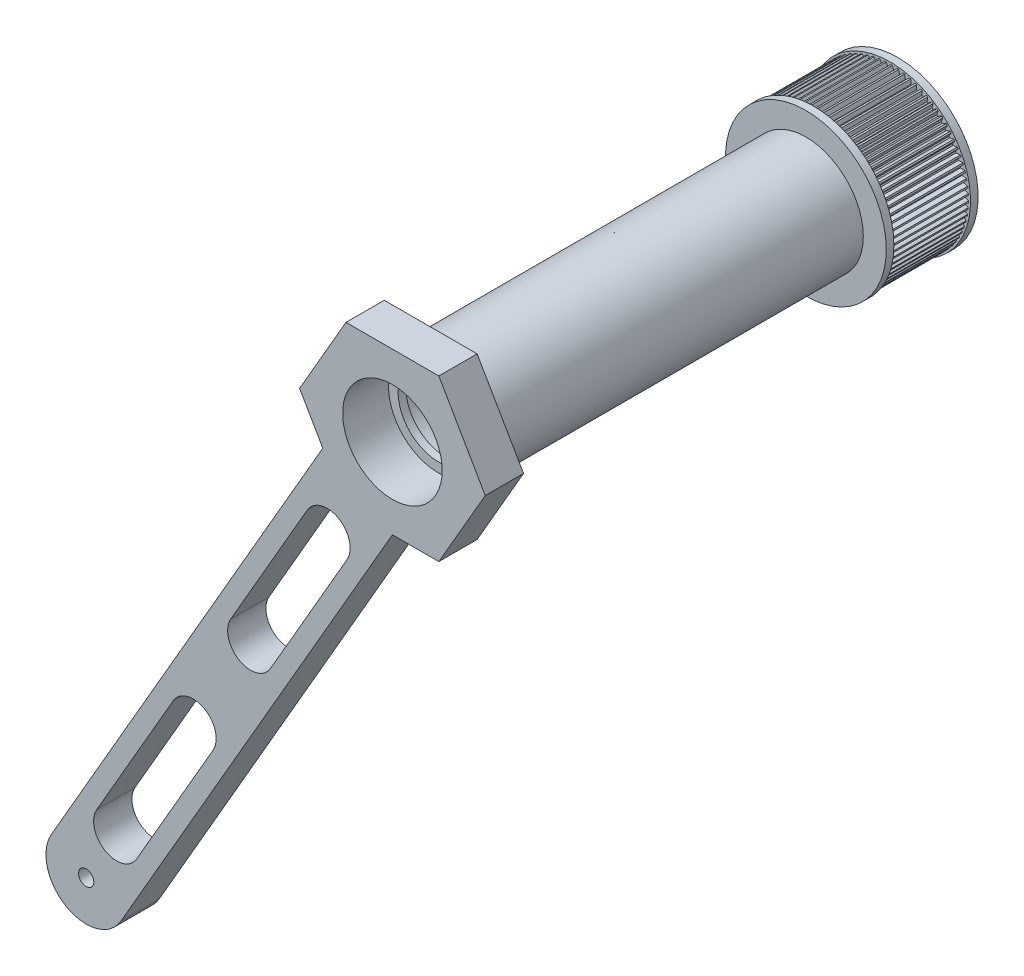
SolidWorks part; units mm, degrees
ref_plane "前视基准面" through (0, 0, 0) normal (0, 0, 1) x (1, 0, 0)
ref_plane "上视基准面" through (0, 0, 0) normal (0, 1, 0) x (1, 0, 0)
ref_plane "右视基准面" through (0, 0, 0) normal (1, 0, 0) x (0, 0, -1)
other "Configuration Table"
sketch "草图1" plane through (0, 0, 0) normal (0, 0, 1) x (1, 0, 0)
  circle A0 centre (0, 0) radius 75
  circle A1 centre (0, 0) radius 65
  dimension "D1" = 150
  dimension "D2" = 10
extrude "凸台-拉伸1" add sketch "草图1" along normal blind 500
sketch "草图2" plane through (0, 0, 0) normal (0, 0, -1) x (-1, 0, 0)
  circle A0 centre (0, 0) radius 96.875
  circle A1 centre (0, 0) radius 90
  dimension "D1" = 193.75
  dimension "D2" = 180
extrude "凸台-拉伸2" add sketch "草图2" along normal blind 100
sketch "草图4" plane through (0, 0, -100) normal (0, 0, -1) x (-1, 0, 0)
  line L0 (0, 0) -> (0, -117.5882) construction
  line L1 (0, 0) -> (42.0407, -115.5058) construction
  line L2 (0, 0) -> (2.3161, -117.9425) construction
  line L3 (0, -100) -> (32.1394, -88.3022) construction
  arc A0 (1.0211, -102.4949) -> (3.0036, -102.456) centre (0, 0) ccw
  circle A1 centre (0, 0) radius 100 construction
  arc A2 (-0.9721, -96.8701) -> (4.7744, -96.7573) centre (0, 0) ccw
  arc A3 (-0.9721, -96.8701) -> (1.0211, -102.4949) centre (32.1394, -88.3022) ccw
  arc A4 (4.7744, -96.7573) -> (3.0036, -102.456) centre (-28.6479, -89.4959) cw
  dimension "D1" = 205
  dimension "D2" = 200
  dimension "D3" = 193.75
  dimension "D4" = 20
  dimension "D5" = 1.125
extrude "凸台-拉伸3" add sketch "草图4" against normal up to surface (100 mm away) up to face at (75, 0, 0)
sketch "草图5" plane through (0, 0, 0) normal (0, 0, 1) x (1, 0, 0)
  circle A0 centre (0, 0) radius 96.875
  circle A1 centre (0, 0) radius 75
extrude "凸台-拉伸4" add sketch "草图5" along normal blind 10
pattern_circular "阵列(圆周)1" count 80 over 360 about axis through (0, 0, -100) along (0, 0, -1) of "凸台-拉伸3"
sketch "草图6" plane through (0, 0, 10) normal (0, 0, 1) x (1, 0, 0)
  circle A0 centre (0, 0) radius 77.5
  circle A1 centre (0, 0) radius 105
  dimension "D1" = 27.5
  dimension "D2" = 210
extrude "凸台-拉伸5" add sketch "草图6" against normal up to surface (10 mm away) up to face at (25.1725, 96.466, 0)
sketch "草图7" plane through (0, 0, -100) normal (0, 0, -1) x (-1, 0, 0)
  circle A0 centre (0, 0) radius 105
  circle A1 centre (0, 0) radius 90
  dimension "D1" = 210
extrude "凸台-拉伸6" add sketch "草图7" along normal blind 10 contours A0 A1 | A0 | A1 region at (102.0302, 0, -100)
sketch "草图8" plane through (0, 0, 500) normal (0, 0, 1) x (1, 0, 0)
  line L0 (0, 0) -> (-400, -692.8203) construction
  line L1 (0, -105) -> (-354.5337, -719.0703)
  line L2 (-90.9327, -52.5) -> (-445.4663, -666.5703)
  line L3 (60.6218, 105) -> (-60.6218, 105)
  line L4 (-60.6218, 105) -> (-121.2436, 0)
  line L5 (-121.2436, 0) -> (-60.6218, -105)
  line L6 (-60.6218, -105) -> (60.6218, -105)
  line L7 (60.6218, -105) -> (121.2436, 0)
  line L8 (121.2436, 0) -> (60.6218, 105)
  circle A0 centre (0, 0) radius 105 construction
  circle A1 centre (0, 0) radius 105 construction
  circle A2 centre (0, 0) radius 65
  arc A3 (-445.4663, -666.5703) -> (-354.5337, -719.0703) centre (-400, -692.8203) ccw
  circle M13 centre (0, 0) radius 75
  dimension "D2" = 800
  dimension "D1" = 130
extrude "凸台-拉伸7" add sketch "草图8" along normal blind 50 separate body contours L7 L8 L3 L4 L5 L6 M13 | L2 A3 L1 L6 L5 region at (-236.851, -410.238, 500) region at (-30.3109, -101.7922, 500)
sketch "草图9" plane through (0, 0, 500) normal (0, 0, 1) x (1, 0, 0)
  circle A0 centre (0, 0) radius 65 construction
  circle A1 centre (0, 0) radius 75
  circle A2 centre (0, 0) radius 75
  circle A3 centre (0, 0) radius 65
  dimension "D1" = 0
extrude "凸台-拉伸8" add sketch "草图9" along normal up to surface (50 mm away) up to face at (75, 0, 550)
sketch "草图10" plane through (0, 0, 550) normal (0, 0, 1) x (1, 0, 0)
  line L0 (1.6995, 2.9436) -> (-316.0028, -547.3329) construction
  line L1 (0, -105) -> (-354.5337, -719.0703) construction
  line L2 (-185.2332, -320.8333) -> (-85.2332, -147.6282) construction
  line L3 (-211.2139, -305.8333) -> (-111.2139, -132.6282)
  line L4 (-159.2524, -335.8333) -> (-59.2524, -162.6282)
  line L5 (-360.2332, -623.9421) -> (-260.2332, -450.7371) construction
  line L6 (-386.2139, -608.9421) -> (-286.2139, -435.7371)
  line L7 (-334.2524, -638.9421) -> (-234.2524, -465.7371)
  line L8 (-177.2668, -412.0352) -> (-268.1995, -359.5352) construction
  line L9 (-90.9327, -52.5) -> (-445.4663, -666.5703) construction
  arc A0 (-211.2139, -305.8333) -> (-159.2524, -335.8333) centre (-185.2332, -320.8333) ccw
  arc A1 (-59.2524, -162.6282) -> (-111.2139, -132.6282) centre (-85.2332, -147.6282) ccw
  arc A2 (-386.2139, -608.9421) -> (-334.2524, -638.9421) centre (-360.2332, -623.9421) ccw
  arc A3 (-234.2524, -465.7371) -> (-286.2139, -435.7371) centre (-260.2332, -450.7371) ccw
  point P7 (-135.2332, -234.2307)
  point P14 (-310.2332, -537.3396)
  point P23 (-326.3019, -620.4384)
  dimension "D1" = 200
  dimension "D2" = 200
  dimension "D3" = 150
  dimension "D4" = 75
  dimension "D5" = 60
  dimension "D6" = 60
extrude "切除-拉伸1" cut sketch "草图10" against normal up to surface (50 mm away) up to face at (75, 0, 500)
sketch "草图11" plane through (0, 0, 550) normal (0, 0, 1) x (1, 0, 0)
  arc A1 (-445.4663, -666.5703) -> (-354.5337, -719.0703) centre (-400, -692.8203) ccw construction
  circle A2 centre (-400, -692.8203) radius 10
  arc A3 (-445.4663, -666.5703) -> (-354.5337, -719.0703) centre (-400, -692.8203) ccw construction
  dimension "D1" = 20
extrude "切除-拉伸2" cut sketch "草图11" against normal through all
sketch "草图12" plane through (0, 0, 0) normal (0, 0, -1) x (-1, 0, 0)
  circle A0 centre (0, 0) radius 52.5
  circle A1 centre (0, 0) radius 65
  dimension "D1" = 105
  dimension "D2" = 130
extrude "凸台-拉伸9" add sketch "草图12" against normal blind 10 from offset 10 offset against normal yes
sketch "草图13" plane through (0, 0, 550) normal (0, 0, 1) x (1, 0, 0)
  circle A0 centre (0, 0) radius 65
  circle A1 centre (0, 0) radius 52.5
  dimension "D1" = 105
  dimension "D2" = 130
extrude "凸台-拉伸10" add sketch "草图13" along normal blind 10 from offset 70 offset against normal yes
